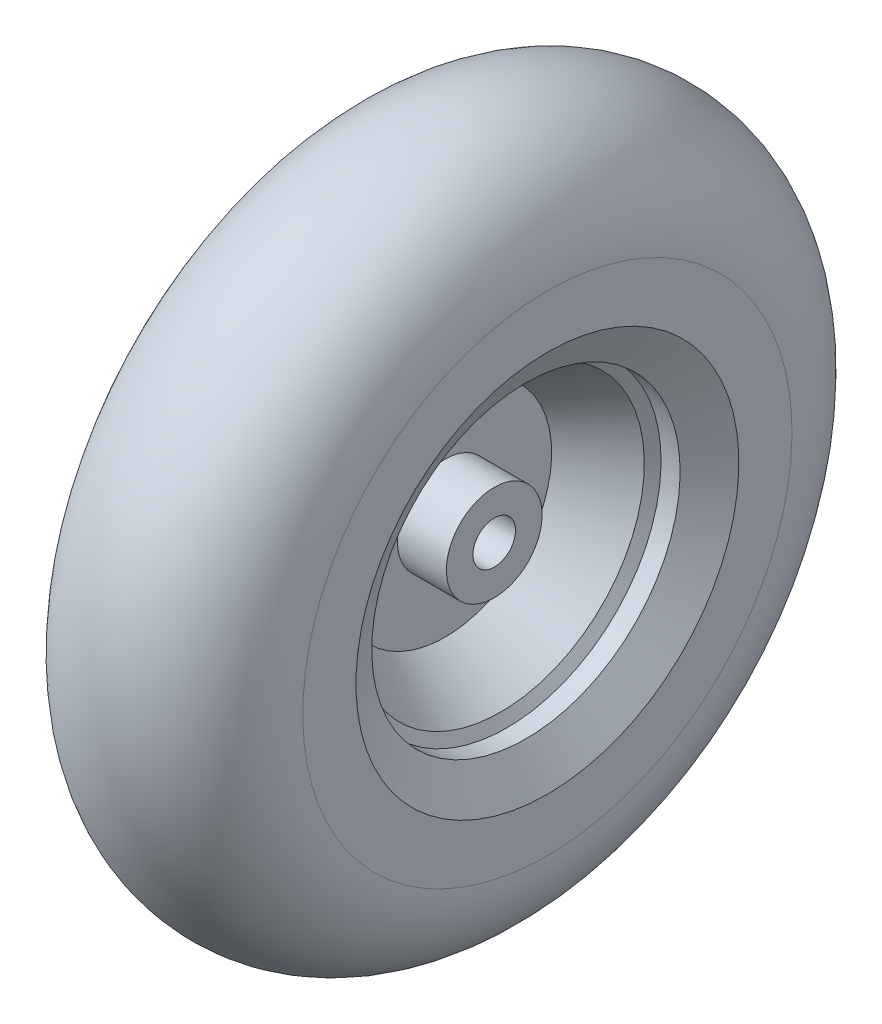
SolidWorks part; units mm, degrees
ref_plane "Front Plane" through (0, 0, 0) normal (0, 0, 1) x (1, 0, 0)
ref_plane "Top Plane" through (0, 0, 0) normal (0, 1, 0) x (1, 0, 0)
ref_plane "Right Plane" through (0, 0, 0) normal (1, 0, 0) x (0, 0, -1)
sketch "Sketch1" plane through (0, 0, 0) normal (0, 0, 1) x (1, 0, 0)
  line L0 (0, 0) -> (0, 165) construction
  line L1 (50, 165) -> (-50, 165) construction
  line L2 (-50, 115) -> (50, 115) construction
  line L3 (50, 165) -> (50, 15) construction
  line L4 (0, 90) -> (50, 90) construction
  line L5 (50, 90) -> (50, 115)
  line L6 (50, 90) -> (39.8964, 72.5)
  line L7 (39.8964, 72.5) -> (30.95, 72.5)
  line L8 (30.95, 72.5) -> (28.0632, 67.5)
  line L9 (28.0632, 67.5) -> (2, 50)
  line L10 (0, 10) -> (25, 10)
  line L11 (25, 10) -> (25, 22.5)
  line L12 (25, 22.5) -> (2, 22.5)
  line L13 (2, 22.5) -> (2, 50)
  line L14 (-50, 115) -> (-50, 90)
  line L15 (-50, 90) -> (-39.8964, 72.5)
  line L16 (-39.8964, 72.5) -> (-30.95, 72.5)
  line L17 (-30.95, 72.5) -> (-28.0632, 67.5)
  line L18 (-28.0632, 67.5) -> (-2, 50)
  line L19 (-2, 50) -> (-2, 22.5)
  line L20 (-2, 22.5) -> (-40, 22.5)
  line L21 (-40, 22.5) -> (-40, 10)
  line L22 (-40, 10) -> (0, 10)
  line L23 (0, 0) -> (-50, 0) construction
  arc A0 (50, 115) -> (-50, 115) centre (0, 115) ccw
  dimension "D3" = 90
  dimension "D1" = 165
  dimension "D2" = 100
  dimension "D4" = 2
  dimension "D5" = 22.5
  dimension "D6" = 10
  dimension "D7" = 25
  dimension "D8" = 30
  dimension "D9" = 72.5
  dimension "D10" = 19.05
  dimension "D11" = 5
  dimension "D12" = 50
  dimension "D13" = 10
revolve "Revolve1" add sketch "Sketch1" angle 360 about L23
ref_axis "Axis1" through (-166.9041, 0, 0) along (1, 0, 0)
ref_plane "Plane1" through (-75, 0, 0) normal (-1, 0, 0) x (0, 0, 1)
ref_point "Point1"
ref_axis "Axis2" through (-75, 0, -37.0326) along (0, 0, 1)
ref_plane "Plane2" through (-72.7385, 12.8258, 0) normal (-0.9848, 0.1736, 0) x (0, 0, 1)
ref_axis "Axis4" through (-92.8544, -101.2575, 0) along (0.1736, 0.9848, 0)
